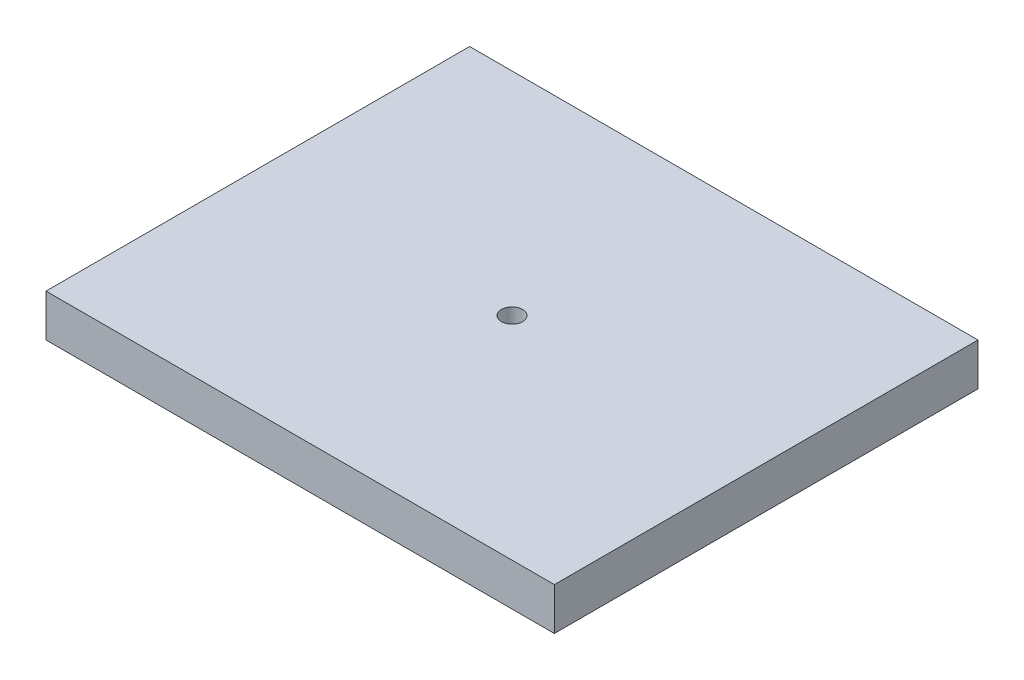
SolidWorks part; units mm, degrees
ref_plane "Front Plane" through (0, 0, 0) normal (0, 0, 1) x (1, 0, 0)
ref_plane "Top Plane" through (0, 0, 0) normal (0, 1, 0) x (1, 0, 0)
ref_plane "Right Plane" through (0, 0, 0) normal (1, 0, 0) x (0, 0, -1)
sketch "Sketch1" plane through (0, 0, 0) normal (0, 1, 0) x (1, 0, 0)
  line L1 (-120, -100) -> (120, -100)
  line L2 (-120, -100) -> (-120, 100)
  line L3 (-120, 100) -> (120, 100)
  line L4 (120, -100) -> (120, 100)
  line L5 (-120, -100) -> (120, 100) construction
  line L6 (-120, 100) -> (120, -100) construction
  point P0 (0, 0)
  dimension "D1" = 240
  dimension "D2" = 200
extrude "Boss-Extrude1" add sketch "Sketch1" along normal mid plane 20
sketch "Sketch2" plane through (0, 10, 0) normal (0, 1, 0) x (1, 0, 0)
  circle A0 centre (0, 0) radius 5
  dimension "D1" = 10
extrude "Cut-Extrude1" cut sketch "Sketch2" against normal through all
